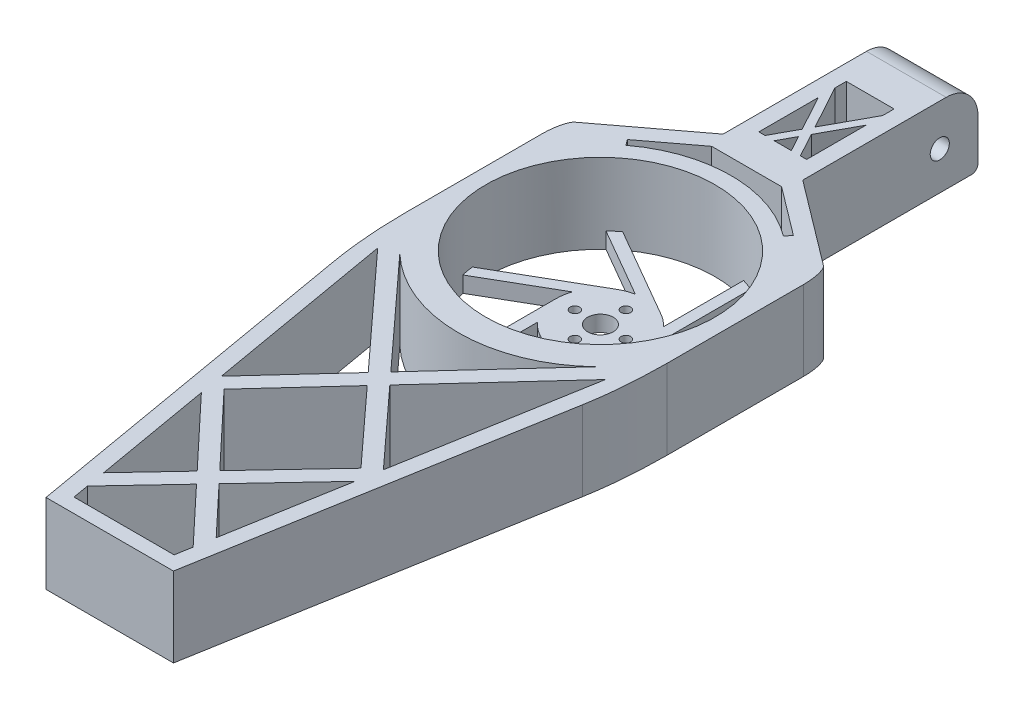
SolidWorks part; units mm, degrees
material "ABS"
ref_plane "Płaszczyzna przednia" through (0, 0, 0) normal (0, 0, 1) x (1, 0, 0)
ref_plane "Płaszczyzna górna" through (0, 0, 0) normal (0, 1, 0) x (1, 0, 0)
ref_plane "Płaszczyzna prawa" through (0, 0, 0) normal (1, 0, 0) x (0, 0, -1)
sketch "Szkic1" plane through (0, 0, 0) normal (0, 1, 0) x (1, 0, 0)
  line L0 (-20.5, -48.6037) -> (-39.5, 60.7732)
  line L1 (-0.5, 106.3963) -> (-0.5, -48.6037) construction
  line L2 (12, 211.3963) -> (-13, 211.3963)
  line L3 (-0.5, 105.3963) -> (-25.1987, 138.1221) construction
  line L4 (19.5, -48.6037) -> (-20.5, -48.6037)
  line L5 (-39.5, 136.3963) -> (-39.5, 60.7732)
  line L6 (38.5, 136.3963) -> (38.5, 60.7732)
  line L7 (-13, 156.3963) -> (-13, 211.3963)
  line L8 (-25.1987, 138.1221) -> (-26.5467, 139.9082)
  line L10 (12, 156.3963) -> (12, 211.3963)
  line L11 (24.1987, 138.1221) -> (25.5467, 139.9082)
  line L12 (-0.5, 105.3963) -> (36.6655, 105.3963) construction
  line L16 (-11.466, 151.2898) -> (10.466, 151.2898)
  line L18 (-0.5, 105.3963) -> (38.5, 105.3963) construction
  line L19 (1.0907, -6.7501) -> (1.0723, -6.7223)
  line L21 (-13, 156.3963) -> (-39.5, 136.3963)
  line L22 (12, 156.3963) -> (38.5, 136.3963)
  line L23 (-11.466, 151.2898) -> (-26.5467, 139.9082)
  line L24 (10.466, 151.2898) -> (25.5467, 139.9082)
  line L26 (-9.988, 152.4054) -> (-36.488, 132.4054) construction
  line L33 (19.5, -48.6037) -> (38.5, 60.7732)
  line L36 (1.1229, -6.7586) -> (1.0907, -6.7501)
  line L46 (-2.1229, -6.7586) -> (-2.0907, -6.7501)
  circle A0 centre (-0.5, 105.3963) radius 36
  circle A1 centre (-0.5, 105.3963) radius 4
  circle A2 centre (-0.5, 97.3963) radius 1.5
  circle A3 centre (-8.5, 105.3963) radius 1.5
  circle A4 centre (-0.5, 113.3963) radius 1.5
  circle A5 centre (7.5, 105.3963) radius 1.5
  arc A6 (24.1987, 138.1221) -> (-25.1987, 138.1221) centre (-0.5, 105.3963) ccw
  circle A9 centre (-0.5, 105.3963) radius 41 construction
  point P9 (-15.5208, -48.1484)
  point P12 (0, 85)
  point P14 (-0.5, 156.3785)
  point P16 (-0.5, -39.3616)
  point P18 (-34.2569, 59.805)
  point P24 (-0.5, 176.9822)
  point P27 (32.5, 54.0178)
  point P34 (-0.5, 105.3963)
  point P41 (-0.5, 148.8753)
  point P44 (-0.5, 211.3963)
  dimension "D6" = 72
  dimension "D5" = 8
  dimension "D8" = 41
  dimension "D4" = 154
  dimension "D12" = 41
  dimension "D13" = 4
  dimension "D14" = 3
  dimension "D15" = 8
  dimension "D16" = 1.0723
  dimension "D17" = 1.0907
  dimension "D10" = 106
  dimension "D3" = 78
  dimension "D9" = 40
  dimension "D11" = 12.5
  dimension "D18" = 1.1229
  dimension "D19" = 20
  dimension "D20" = 5
  dimension "D21" = 7.5
  dimension "D22" = 10.466
  dimension "D23" = 25.5467
  dimension "D24" = 60.7732
  dimension "D25" = 85
  dimension "D26" = 97.3963
  dimension "D28" = 2.0907
  dimension "D29" = 2.1229
  dimension "D30" = 148.8753
  dimension "D31" = 156.3785
  dimension "D32" = 176.9822
  dimension "D33" = 6.7223
  dimension "D34" = 39.3616
  dimension "D7" = 5
extrude "Dodanie-wyciągnięcie1" add sketch "Szkic1" along normal blind 5 contours A0 A5 A4 A3 A2 A1 | L5 L4 L6 A0 A6 L16 region at (-0.5, 0, -57.1384) region at (-35.4818, 0, -105.3963)
extrude "Dodanie-wyciągnięcie2" add sketch "Szkic1<3>" along normal blind 25 contours L5 L4 L6 A0 A6 L16 region at (-0.5, 0, -57.1384)
sketch "Szkic1<3>" plane through (0, 0, 0) normal (0, 1, 0) x (1, 0, 0) same geometry as "Szkic1"
fillet "Zaokrąglenie1" radius 10 1 edges at (-0.5, 25, -211.3963)
fillet "Zaokrąglenie2" radius 2 1 edges at (-0.5, 0, -211.3963)
sketch "Szkic3" plane through (-13, 0, 0) normal (-1, 0, 0) x (0, 0, 1)
  line L0 (-156.3963, 0) -> (-209.3963, 0) construction
  line L1 (-211.3963, 15) -> (-211.3963, 2) construction
  circle A0 centre (-199.3963, 12) radius 3
  dimension "D1" = 6
  dimension "D2" = 12
  dimension "D3" = 12
extrude "Wytnij-wyciągnięcie2" cut sketch "Szkic3" against normal through all
sketch "Szkic4" plane through (0, 5, 0) normal (0, 1, 0) x (1, 0, 0)
  line L0 (13.5, 105.3963) -> (13.5, 138.5626)
  line L1 (10, 139.831) -> (10, 114.6565)
  line L2 (34.5713, 113.5204) -> (12.7695, 100.9331)
  line L3 (6.5, 93.272) -> (35.2228, 109.8551)
  line L4 (24.0713, 79.0857) -> (2.2695, 91.673)
  line L5 (-7.5, 93.272) -> (21.2228, 76.6888)
  line L6 (-11, 70.9616) -> (-11, 96.1362)
  line L7 (-14.5, 105.3963) -> (-14.5, 72.2301)
  line L8 (-35.5713, 97.2722) -> (-13.7695, 109.8595)
  line L9 (-7.5, 117.5207) -> (-36.2228, 100.9376)
  line L10 (-25.0713, 131.707) -> (-3.2695, 119.1197)
  line L11 (6.5, 117.5207) -> (-22.2228, 134.1038)
  circle A0 centre (-0.5, 105.3963) radius 14
  circle A1 centre (-0.5, 105.3963) radius 36 construction
  circle A2 centre (-0.5, 105.3963) radius 36
  point P32 (-0.5, 105.3963)
  circle M3 centre (-0.5, 105.3963) radius 36
  dimension "D1" = 28
  dimension "D4" = 72
  dimension "D2" = 3.5
  dimension "D3" = 6
extrude "Wytnij-wyciągnięcie3" cut sketch "Szkic4" against normal through all contours A0 L10 L9 M3 | A0 L1 L11 M3 | A0 L2 L0 M3 | A0 L4 L3 M3 | A0 L6 L5 M3 | A0 L8 L7 M3 region at (21.3644, 5, -119.4561) region at (-1.7439, 5, -131.3613) region at (22.6083, 5, -93.4911) region at (-23.6083, 5, -117.3016) region at (0.7439, 5, -79.4313) region at (-22.3644, 5, -91.3366)
sketch "Szkic5" plane through (0, 25, 0) normal (0, 1, 0) x (1, 0, 0)
  line L0 (-0.5, 201.3963) -> (-0.5, 151.2898) construction
  line L1 (12, 201.3963) -> (-13, 201.3963) construction
  line L2 (-11.466, 151.2898) -> (10.466, 151.2898) construction
  line L3 (12, 156.3963) -> (12, 201.3963) construction
  line L4 (-8, 162.6176) -> (7, 162.6176)
  line L5 (-8, 162.6176) -> (-8, 190.0686)
  line L6 (-8, 190.0686) -> (7, 190.0686)
  line L7 (7, 162.6176) -> (7, 190.0686)
  line L8 (-8, 162.6176) -> (7, 190.0686) construction
  line L9 (-8, 190.0686) -> (7, 162.6176) construction
  line L10 (-8, 181.2634) -> (2.1886, 162.6176)
  line L11 (-3.1886, 162.6176) -> (7, 181.2634)
  line L12 (-9.9625, 190.0686) -> (7, 159.0261)
  line L13 (-8, 159.0261) -> (8.9625, 190.0686)
  line L15 (-11.7051, 188.044) -> (3.2949, 160.593) construction
  line L16 (-6.4887, 161.7918) -> (8.5113, 189.2428) construction
  line L17 (-4.2949, 160.593) -> (10.7051, 188.044) construction
  line L18 (-9.5113, 189.2428) -> (5.4887, 161.7918) construction
  point P6 (-0.5, 176.3431)
  point P14 (12, 178.8963)
  dimension "D1" = 5
extrude "Wytnij-wyciągnięcie4" cut sketch "Szkic5" against normal through all contours L5 L13 L10 | L12 L13 L6 | L11 L12 L7 | L11 L4 L10 region at (-0.5, 25, -164.2577) region at (-5.8994, 25, -170.6249) region at (4.8994, 25, -170.6249) region at (-0.5, 25, -184.0906)
sketch "Szkic6" plane through (0, 25, 0) normal (0, 1, 0) x (1, 0, 0)
  line L0 (-0.5, 69.3963) -> (-0.5, -48.6037) construction
  line L1 (19.5, -48.6037) -> (-20.5, -48.6037) construction
  line L2 (-20.5, -48.6037) -> (19.5, -48.6037)
  line L3 (19.5, -48.6037) -> (38.5, 60.7732)
  line L4 (-39.5, 136.3963) -> (-39.5, 60.7732) construction
  line L5 (-39.5, 60.7732) -> (-20.5, -48.6037)
  line L6 (-36.243, 71.2381) -> (-16.2068, -44.1037)
  line L7 (35.243, 71.2381) -> (15.2068, -44.1037)
  line L8 (-24.6092, 4.2661) -> (-3.9318, -17.7213)
  line L9 (-36.243, 71.2381) -> (-3.8901, 35.9142)
  line L10 (35.243, 71.2381) -> (2.8901, 35.9142)
  line L11 (-0.5, 32.2128) -> (20.976, 8.7646)
  line L12 (20.976, 8.7646) -> (-0.5, -14.0721)
  line L13 (30.2624, 73.203) -> (-0.5, 39.6157)
  line L14 (-24.6092, 4.2661) -> (-3.9318, -17.7213)
  line L15 (-31.2624, 73.203) -> (-0.5, 39.6157)
  line L16 (23.6092, 4.2661) -> (2.9318, -17.7213)
  line L17 (2.8901, 35.9142) -> (24.9272, 11.8534)
  line L18 (-21.976, 8.7646) -> (-0.5, -14.0721)
  line L19 (-3.8901, 35.9142) -> (-25.9272, 11.8534)
  line L20 (-0.5, 32.2128) -> (-21.976, 8.7646)
  line L21 (-16.2068, -44.1037) -> (15.2068, -44.1037)
  line L23 (-20.5, -48.6037) -> (-39.5, 60.7732) construction
  line L24 (2.9318, -17.7213) -> (17.1613, -32.8523)
  line L25 (-3.9318, -17.7213) -> (-18.1613, -32.8523)
  line L26 (-0.5, -21.3706) -> (16.0912, -39.0129)
  line L27 (-0.5, -21.3706) -> (-17.0912, -39.0129)
  line L28 (-0.5, -21.3706) -> (14.805, -37.6453)
  circle A0 centre (-0.5, 105.3963) radius 36 construction
  arc A1 (-31.2624, 73.203) -> (30.2624, 73.203) centre (-0.5, 105.3963) ccw
  point P24 (-15.805, -37.6453)
  dimension "D3" = 44.5279
  dimension "D1" = 5
  dimension "D2" = 4.5
  dimension "D4" = 3.257
  dimension "D5" = 8.2376
  dimension "D6" = 13.5728
  dimension "D7" = 14.8908
  dimension "D8" = 17.524
  dimension "D9" = 21.3387
  dimension "D10" = 22.4088
  dimension "D11" = 23.695
  dimension "D12" = 35.6099
extrude "Wytnij-wyciągnięcie5" cut sketch "Szkic6" against normal through all contours L19 L9 L6 | L0 L20 L18 | L25 L8 L6 | L0 L27 L6 L21 | L26 L0 L21 L7 | L16 L24 L7 | L11 L0 L12 | L10 L17 L7 | A1 L0 L13 | L0 A1 L15 region at (21.0201, 25, -39.6686) region at (14.5674, 25, 15.4359) region at (-22.0201, 25, -39.6686) region at (-15.5674, 25, 15.4359) region at (5.9462, 25, 36.1545) region at (-6.9462, 25, 36.1545) region at (6.6587, 25, -8.9684) region at (-7.6587, 25, -8.9684) region at (-9.1935, 25, -55.6824) region at (8.1935, 25, -55.6824)
sketch "Szkic7" plane through (0, 0, 0) normal (0, -1, 0) x (1, 0, 0)
  line L0 (19.5, 48.6037) -> (38.5, -60.7732) construction
  line L1 (-39.5, -136.3963) -> (-37.7057, -137.7505)
  line L2 (12, -156.3963) -> (38.5, -136.3963) construction
  line L3 (40.5, -85.3408) -> (40.5, -128.1784)
  line L4 (38.5, -60.7732) -> (38.5, -136.3963)
  line L5 (-0.5, -32.2128) -> (-0.5, -211.3963) construction
  line L6 (-13, -211.3963) -> (12, -211.3963) construction
  line L7 (-39.5, -60.7732) -> (-39.5, -136.3963)
  line L8 (-41.5, -85.3408) -> (-41.5, -128.1784)
  arc A0 (13.5, -138.5626) -> (34.5713, -113.5204) centre (-0.5, -105.3963) ccw construction
  ellipse E0 centre (28.3928, -81.6144) end of major axis (29.5113, -125.279) minor radius 12.0593 (40.5, -85.3408) -> (38.5, -60.7732) ccw
  ellipse E1 centre (38.5024, -129.6941) end of major axis (38.9814, -122.8258) minor radius 1.944 (38.5, -136.3963) -> (40.5, -128.1784) ccw
  ellipse E2 centre (-39.5024, -129.6941) end of major axis (-39.9814, -122.8258) minor radius 1.944 (-39.5, -136.3963) -> (-41.5, -128.1784) cw
  ellipse E3 centre (-29.3928, -81.6144) end of major axis (-30.5113, -125.279) minor radius 12.0593 (-41.5, -85.3408) -> (-39.5, -60.7732) cw
  point P21 (38.5, -60.7732)
  dimension "D1" = 41
extrude "Dodanie-wyciągnięcie3" add sketch "Szkic7" against normal blind 25 contours L3 E1 L4 E0 | E2 L8 E3 L7
